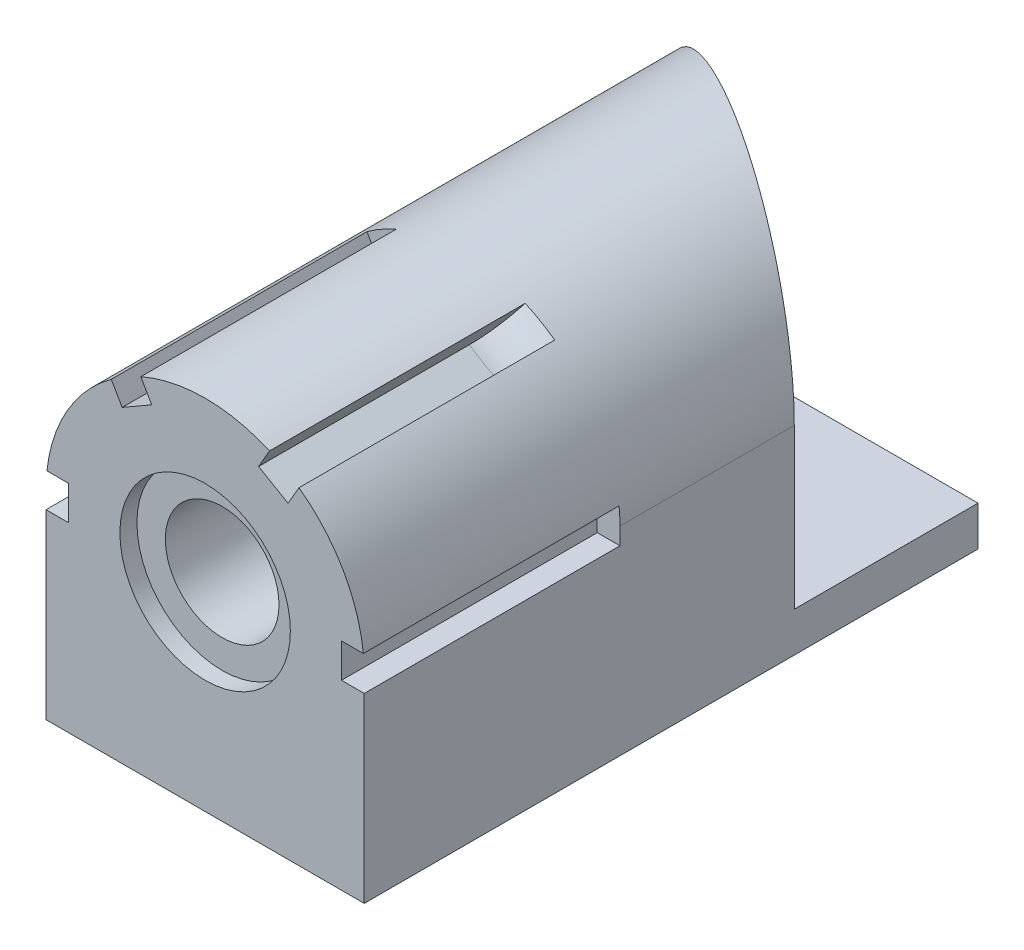
SolidWorks part; units mm, degrees
ref_plane "前视基准面" through (0, 0, 0) normal (0, 0, 1) x (1, 0, 0)
ref_plane "上视基准面" through (0, 0, 0) normal (0, 1, 0) x (1, 0, 0)
ref_plane "右视基准面" through (0, 0, 0) normal (1, 0, 0) x (0, 0, -1)
other "Configuration Table"
sketch "草图1" plane through (0, 0, 0) normal (0, 0, 1) x (1, 0, 0)
  line L0 (0, 84.0536) -> (0, -63.1072) construction
  line L1 (-28, 0) -> (28, 0)
  line L2 (-28, 35) -> (-28, 0)
  line L3 (28, 35) -> (28, 0)
  arc A0 (28, 35) -> (-28, 35) centre (0, 35) ccw
  circle A1 centre (0, 35) radius 10
  dimension "D2" = 56
  dimension "D3" = 20
  dimension "D1" = 35
extrude "凸台-拉伸1" add sketch "草图1" against normal blind 108
sketch "草图2" plane through (0, 0, 0) normal (0, 1, 0) x (1, 0, 0)
  line L0 (-28, 108) -> (28, 75.6684)
  line L1 (28, 108) -> (28, 0) construction
  line L2 (28, 108) -> (-28, 108) construction
  line L3 (28, 108) -> (28, 75.6684)
  line L4 (28, 108) -> (-28, 108)
  dimension "D1" = 30
extrude "切除-拉伸1" cut sketch "草图2" along normal through all from offset 7
sketch "草图3" plane through (0, 0, 0) normal (0, 0, 1) x (1, 0, 0)
  circle A0 centre (0, 35) radius 15
  circle A1 centre (0, 35) radius 10 construction
  circle A2 centre (0, 35) radius 10
  dimension "D1" = 30
extrude "切除-拉伸2" cut sketch "草图3" against normal blind 3
sketch "草图4" plane through (0, 0, 0) normal (0, 0, 1) x (1, 0, 0)
  line L0 (-45.8317, 35) -> (45.8317, 35) construction
  line L2 (-28.7273, 38) -> (-24, 38)
  line L3 (-28.7273, 38) -> (-28.7273, 32)
  line L4 (-28.7273, 32) -> (-24, 32)
  line L5 (-24, 38) -> (-24, 32)
  line L6 (-28.7273, 38) -> (-24, 32) construction
  line L7 (-28.7273, 32) -> (-24, 38) construction
  point P3 (-26.3636, 35)
  point P9 (0, 35)
  dimension "D1" = 6
  dimension "D2" = 24
sketch "草图5" plane through (0, 0, 0) normal (0, 0, 1) x (1, 0, 0)
extrude "切除-拉伸4" cut sketch "草图4" against normal blind 45
pattern_circular "阵列(圆周)2" count 4 over 180 about axis through (0, 35, -108) along (0, 0, 1) of "切除-拉伸4" reverse direction yes
fillet "圆角1" radius 10 1 edges at (12, 55.7846, -45)
